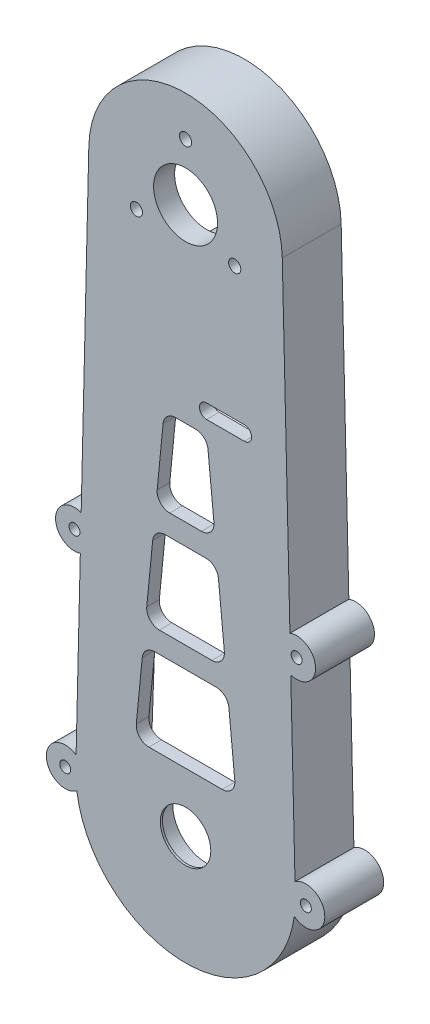
SolidWorks part; units mm, degrees
ref_plane "Front Plane" through (0, 0, 0) normal (0, 0, 1) x (1, 0, 0)
ref_plane "Top Plane" through (0, 0, 0) normal (0, 1, 0) x (1, 0, 0)
ref_plane "Right Plane" through (0, 0, 0) normal (1, 0, 0) x (0, 0, -1)
ref_plane "Plane1" through (0, 0, 344.5) normal (0, 0, 1) x (1, 0, 0)
sketch "Sketch1" plane through (0, 0, 344.5) normal (0, 0, 1) x (1, 0, 0)
  line L0 (277.0065, 300.5482) -> (273.9088, 170.6221)
  line L1 (326.0912, 170.6221) -> (322.9935, 300.5482)
  line L2 (305, 258.3) -> (314, 258.3)
  line L3 (314, 261.7) -> (305, 261.7)
  line L4 (294.6613, 252.2924) -> (293.2574, 237.9591)
  line L5 (296.2431, 234.6667) -> (303.7569, 234.6667)
  line L6 (306.7426, 237.9591) -> (305.3387, 252.2924)
  line L7 (302.353, 255) -> (297.647, 255)
  line L8 (292.1801, 226.9591) -> (290.7762, 212.6258)
  line L9 (293.762, 209.3333) -> (306.238, 209.3333)
  line L10 (309.2238, 212.6258) -> (307.8199, 226.9591)
  line L11 (304.8342, 229.6667) -> (295.1658, 229.6667)
  line L12 (289.6989, 201.6258) -> (288.2951, 187.2924)
  line L13 (291.2808, 184) -> (308.7192, 184)
  line L14 (311.7049, 187.2924) -> (310.3011, 201.6258)
  line L15 (307.3154, 204.3333) -> (292.6846, 204.3333)
  arc A0 (273.9088, 170.6221) -> (326.0912, 170.6221) centre (300, 170) ccw
  arc A1 (322.9935, 300.5482) -> (277.0065, 300.5482) centre (300, 300) ccw
  circle A2 centre (300, 170) radius 6
  arc A3 (314, 258.3) -> (314, 261.7) centre (314, 260) ccw
  arc A4 (305, 261.7) -> (305, 258.3) centre (305, 260) ccw
  circle A5 centre (300, 313.5) radius 1.45
  circle A6 centre (288.3087, 293.25) radius 1.45
  circle A7 centre (311.6913, 293.25) radius 1.45
  arc A8 (297.647, 255) -> (294.6613, 252.2924) centre (297.647, 252) ccw
  arc A9 (293.2574, 237.9591) -> (296.2431, 234.6667) centre (296.2431, 237.6667) ccw
  arc A10 (303.7569, 234.6667) -> (306.7426, 237.9591) centre (303.7569, 237.6667) ccw
  arc A11 (305.3387, 252.2924) -> (302.353, 255) centre (302.353, 252) ccw
  arc A12 (295.1658, 229.6667) -> (292.1801, 226.9591) centre (295.1658, 226.6667) ccw
  arc A13 (290.7762, 212.6258) -> (293.762, 209.3333) centre (293.762, 212.3333) ccw
  arc A14 (306.238, 209.3333) -> (309.2238, 212.6258) centre (306.238, 212.3333) ccw
  arc A15 (307.8199, 226.9591) -> (304.8342, 229.6667) centre (304.8342, 226.6667) ccw
  arc A16 (292.6846, 204.3333) -> (289.6989, 201.6258) centre (292.6846, 201.3333) ccw
  arc A17 (288.2951, 187.2924) -> (291.2808, 184) centre (291.2808, 187) ccw
  arc A18 (308.7192, 184) -> (311.7049, 187.2924) centre (308.7192, 187) ccw
  arc A19 (310.3011, 201.6258) -> (307.3154, 204.3333) centre (307.3154, 201.3333) ccw
extrude "Boss-Extrude1" add sketch "Sketch1" along normal blind 3
ref_plane "Plane2" through (0, 0, 342.5) normal (0, 0, 1) x (1, 0, 0)
sketch "Sketch2" plane through (0, 0, 342.5) normal (0, 0, 1) x (1, 0, 0)
  circle A0 centre (300, 300) radius 20
  circle A1 centre (300, 313.5) radius 1.45
  circle A2 centre (288.3087, 293.25) radius 1.45
  circle A3 centre (311.6913, 293.25) radius 1.45
extrude "Boss-Extrude2" add sketch "Sketch2" along normal blind 2
sketch "Sketch3" plane through (0, 0, 342.5) normal (0, 0, 1) x (1, 0, 0)
  circle A0 centre (300, 170) radius 12
  circle A1 centre (300, 170) radius 6
extrude "Boss-Extrude3" add sketch "Sketch3" along normal blind 2
ref_plane "Plane3" through (0, 0, 333.5) normal (0, 0, 1) x (1, 0, 0)
sketch "Sketch4" plane through (0, 0, 333.5) normal (0, 0, 1) x (1, 0, 0)
  line L0 (277.0065, 300.5482) -> (273.9088, 170.6221)
  line L1 (326.0912, 170.6221) -> (322.9935, 300.5482)
  line L2 (282.511, 300.619) -> (277.9152, 170.7817)
  line L3 (322.0848, 170.7817) -> (317.489, 300.619)
  arc A0 (273.9088, 170.6221) -> (326.0912, 170.6221) centre (300, 170) ccw
  arc A1 (322.9935, 300.5482) -> (277.0065, 300.5482) centre (300, 300) ccw
  arc A2 (277.9152, 170.7817) -> (322.0848, 170.7817) centre (300, 170) ccw
  arc A3 (317.489, 300.619) -> (282.511, 300.619) centre (300, 300) ccw
extrude "Boss-Extrude4" add sketch "Sketch4" along normal blind 11
sketch "Sketch5" plane through (0, 0, 333.5) normal (0, 0, 1) x (1, 0, 0)
  circle A0 centre (312.1244, 307) radius 4
  circle A1 centre (312.1244, 307) radius 1.3
extrude "Boss-Extrude5" add sketch "Sketch5" along normal blind 9
sketch "Sketch6" plane through (0, 0, 333.5) normal (0, 0, 1) x (1, 0, 0)
  circle A0 centre (287.8756, 307) radius 4
  circle A1 centre (287.8756, 307) radius 1.3
extrude "Boss-Extrude6" add sketch "Sketch6" along normal blind 9
sketch "Sketch7" plane through (0, 0, 333.5) normal (0, 0, 1) x (1, 0, 0)
  circle A0 centre (300, 286) radius 4
  circle A1 centre (300, 286) radius 1.3
extrude "Boss-Extrude7" add sketch "Sketch7" along normal blind 9
sketch "Sketch8" plane through (0, 0, 333.5) normal (0, 0, 1) x (1, 0, 0)
  circle A0 centre (273.5932, 220) radius 4.5
  circle A1 centre (273.5932, 220) radius 1.3
extrude "Boss-Extrude8" add sketch "Sketch8" along normal blind 14
sketch "Sketch9" plane through (0, 0, 333.5) normal (0, 0, 1) x (1, 0, 0)
  circle A0 centre (326.4068, 220) radius 4.5
  circle A1 centre (326.4068, 220) radius 1.3
extrude "Boss-Extrude9" add sketch "Sketch9" along normal blind 14
sketch "Sketch10" plane through (0, 0, 333.5) normal (0, 0, 1) x (1, 0, 0)
  circle A0 centre (271.4014, 170) radius 4.5
  circle A1 centre (271.4014, 170) radius 1.3
extrude "Boss-Extrude10" add sketch "Sketch10" along normal blind 14
sketch "Sketch11" plane through (0, 0, 333.5) normal (0, 0, 1) x (1, 0, 0)
  circle A0 centre (328.5986, 170) radius 4.5
  circle A1 centre (328.5986, 170) radius 1.3
extrude "Boss-Extrude11" add sketch "Sketch11" along normal blind 14
sketch "Sketch12" plane through (0, 0, 342.5) normal (0, 0, 1) x (1, 0, 0)
  circle A0 centre (300, 300) radius 7.6
extrude "Cut-Extrude1" cut sketch "Sketch12" along normal blind 5
sketch "Sketch13" plane through (0, 0, 342.5) normal (0, 0, 1) x (1, 0, 0)
  circle A0 centre (300, 170) radius 8.05
extrude "Cut-Extrude2" cut sketch "Sketch13" along normal blind 4.5
ref_plane "Plane4" through (300, 0, 0) normal (1, 0, 0) x (0, 0, -1)
ref_plane "Plane5" through (0, 300, 0) normal (0, 1, 0) x (1, 0, 0)
ref_axis "HIP_AXIS" through (300, 300, 348.2) along (0, 0, -1)
ref_plane "Plane6" through (0, 170, 0) normal (0, 1, 0) x (1, 0, 0)
ref_axis "KNEE_AXIS" through (300, 170, 348.2) along (0, 0, -1)
